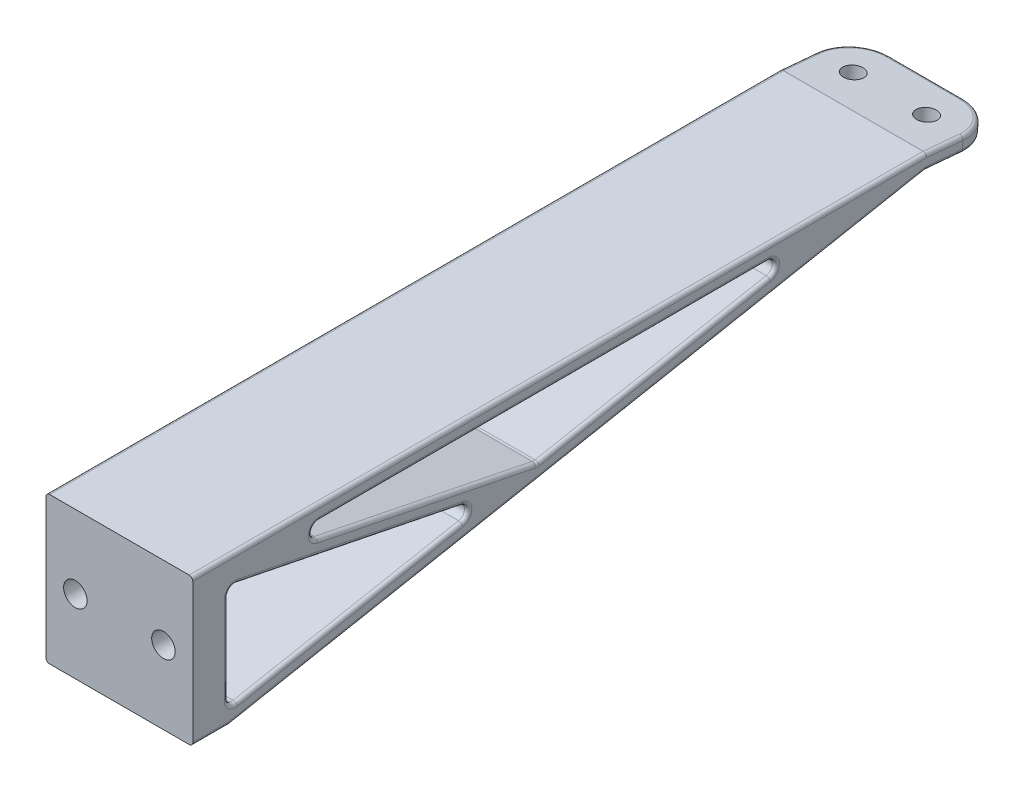
SolidWorks part; units mm, degrees
note: '?' marks a value the reader was unsure of. The reader was unsure of these and kept them because the rebuilt part matched: shared geometry of "Sketch3<3>".
ref_plane "Front Plane" through (0, 0, 0) normal (0, 0, 1) x (1, 0, 0)
ref_plane "Top Plane" through (0, 0, 0) normal (0, 1, 0) x (1, 0, 0)
ref_plane "Right Plane" through (0, 0, 0) normal (1, 0, 0) x (0, 0, -1)
ref_axis "X" through (-88.99, 0, 0) along (1, 0, 0)?
ref_axis "Y" through (0, 55, 0) along (0, -1, 0)?
ref_axis "Z" through (0, 0, -88.99) along (0, 0, 1)?
sketch "Sketch1" plane through (0, 0, 0) normal (1, 0, 0) x (0, 0, -1)
  line L1 (99.8257, 18.0076) -> (109.7876, 17.1361)
  line L2 (109.7876, 17.1361) -> (109.9619, 19.1284)
  line L3 (109.9619, 19.1284) -> (100, 20)
  line L4 (100, 20) -> (0, 20)
  line L5 (0, 20) -> (0, 0)
  line L6 (0, 0) -> (5, 0)
  line L7 (5, 0) -> (99.8257, 18.0076)
  line L8 (89.0657, 18) -> (2, 18)
  line L9 (2, 18) -> (2, 17.0099)
  line L11 (4.8118, 2) -> (89.0657, 18)
  line L12 (89.0657, 18) -> (89.0657, 18)
  line L13 (89.0657, 18) -> (89.0657, 18)
  line L14 (89.0657, 18) -> (89.0657, 18)
  line L15 (2, 17.0099) -> (41.7248, 9.0099)
  line L16 (7.2139, 18) -> (46.9387, 10)
  line L17 (4.8118, 16.4436) -> (4.8118, 2)
  line L19 (2, 18) -> (2, 2) construction
  line L20 (2, 2) -> (4.8118, 2) construction
  point P19 (46.9387, 10)
  point P22 (0, 0)
  dimension "D1" = 2
  dimension "D2" = 10
  dimension "D3" = 100
  dimension "D4" = 20
  dimension "D5" = 5
  dimension "D6" = 5
  dimension "D8" = 2
  dimension "D7" = 2
extrude "Boss-Extrude1" add sketch "Sketch1" along normal mid plane 20
fillet "Fillet1" radius 1 6 edges at (0, 18, -89.0657) (0, 10, -46.9387) (0, 9.0099, -41.7248) (0, 18, -7.2139) (0, 16.4436, -4.8118) (0, 2, -4.8118)
sketch "Sketch2" plane through (0, 28.5305, -2.4961) normal (0, 0.9962, -0.0872) x (1, 0, 0)
  line L0 (0, 107.8764) -> (0, 102.8764) construction
  line L1 (10, 107.8764) -> (-10, 107.8764) construction
  line L2 (0, 102.8764) -> (-5, 102.8764) construction
  line L3 (0, 102.8764) -> (5, 102.8764) construction
  line L4 (0, 102.8764) -> (0, 97.8764) construction
  line L5 (10, 97.8764) -> (-10, 97.8764) construction
  circle A0 centre (-5, 102.8764) radius 1.35
  circle A1 centre (5, 102.8764) radius 1.35
  dimension "D1" = 5
  dimension "D2" = 2.7
extrude "Cut-Extrude1" cut sketch "Sketch2" against normal through all
fillet "Fillet2" radius 5 2 edges at (-10, 18.1322, -109.8748) (10, 18.1322, -109.8748)
fillet "Fillet3" radius 0.5 43 edges at (10, 10.019, -46.9388) (-10, 10.019, -46.9388) (10, 13.0292, -31.8972) (-10, 13.0292, -31.8972) (10, 17.0992, -16.2498) (-10, 17.0992, -16.2498) (-10, 18, -47.8423) (10, 18, -47.8423) (10, 17.0937, -79.4354) (-10, 17.0937, -79.4354) (10, 13.1107, -21.3615) (10, 9.0331, -37.5165) (-10, 13.1107, -21.3615) (-10, 9.0331, -37.5165) (10, 17.7897, -102.3162) (8.5355, 17.2637, -108.3287) (-10, 17.7897, -102.3162) (-8.5355, 17.2637, -108.3287) (10, 19.7821, -102.4905) (8.5355, 19.2561, -108.5031) (-10, 19.7821, -102.4905) (-8.5355, 19.2561, -108.5031) (10, 13.027, -62.8787) (-10, 13.027, -62.8787) (10, 5.1408, -21.3507) (-10, 5.1408, -21.3507) (0, 0, -5) (10, 9.0038, -52.4128) (0, 18.0076, -99.8257) (-10, 9.0038, -52.4128) (0, 17.1361, -109.7876) (0, 19.1284, -109.9619) (10, 20, -50) (-10, 20, -50) (-10, 0, -2.5) (10, 0, -2.5) (0, 20, -100) (10, 9.215, -4.8118) (10, 15.9959, -5.1783) (-10, 9.215, -4.8118) (-10, 15.9959, -5.1783) (10, 2.4375, -5.174) (-10, 2.4375, -5.174)
sketch "Sketch3" plane through (0, 0, -4.8118) normal (0, 0, -1) x (-1, 0, 0)
  line L1 (-9, 8.2679) -> (-6, 6.5359)
  line L2 (-6, 6.5359) -> (-3, 8.2679)
  line L3 (-3, 8.2679) -> (-3, 11.7321)
  line L4 (-3, 11.7321) -> (-6, 13.4641)
  line L5 (-6, 13.4641) -> (-9, 11.7321)
  line L6 (-9, 11.7321) -> (-9, 8.2679)
  line L7 (6, 6.5359) -> (9, 8.2679)
  line L8 (9, 8.2679) -> (9, 11.7321)
  line L9 (9, 11.7321) -> (6, 13.4641)
  line L10 (6, 13.4641) -> (3, 11.7321)
  line L11 (3, 11.7321) -> (3, 8.2679)
  line L12 (3, 8.2679) -> (6, 6.5359)
  circle A0 centre (-6, 10) radius 1.6 construction
  circle A1 centre (6, 10) radius 1.6 construction
  circle A2 centre (-6, 10) radius 1.6 construction
  circle A3 centre (6, 10) radius 1.6 construction
  circle A4 centre (-6, 10) radius 1.6
  circle A5 centre (6, 10) radius 1.6
  circle A6 centre (-6, 10) radius 3 construction
  circle A7 centre (6, 10) radius 3 construction
  dimension "D1" = 6
  dimension "D2" = 3.2
extrude "Cut-Extrude2" cut sketch "Sketch3" against normal through all contours A4 | A5
extrude "Cut-Extrude3" cut sketch "Sketch3<3>" against normal offset from surface (1.8118 mm away) 3 up to face at (6, 11.6, 0)
sketch "Sketch3<3>" plane through (0, 0, -4.8118) normal (0, 0, -1) x (-1, 0, 0) same geometry as "Sketch3"
